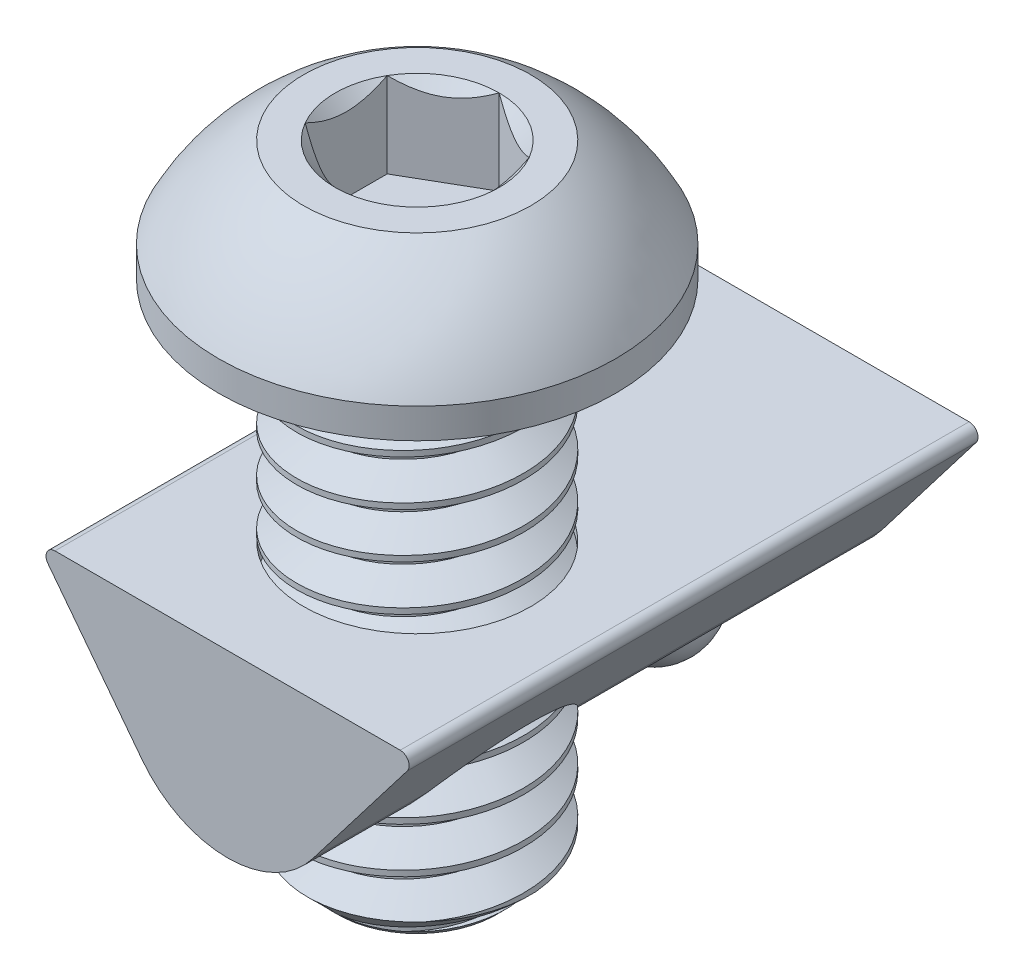
SolidWorks part; units mm, degrees
ref_plane "Front Plane" through (0, 0, 0) normal (0, 0, 1) x (1, 0, 0)
ref_plane "Top Plane" through (0, 0, 0) normal (0, 1, 0) x (1, 0, 0)
ref_plane "Right Plane" through (0, 0, 0) normal (1, 0, 0) x (0, 0, -1)
sketch "Sketch1" plane through (0, 0, 0) normal (0, 1, 0) x (1, 0, 0)
  circle A0 centre (0, 0) radius 3.175
  point P2 (3.175, 0)
  point P3 (-3.175, 0)
  dimension "D1" = 6.35
extrude "Boss-Extrude1" add sketch "Sketch1" against normal blind 14.2875
sketch "Sketch2" plane through (0, -14.2875, 0) normal (0, -1, 0) x (1, 0, 0)
  circle A1 centre (0, 0) radius 3.175
  circle A2 centre (0, 0) radius 3.175
  point P0 (0, -3.175)
  dimension "D1" = 0
curve "Helix/Spiral1" pitch 1.27 height 15.5575 turns 12.25
sketch "Sketch3" plane through (0, 0, 0) normal (1, 0, 0) x (0, 0, -1)
  line L0 (3.3125, -14.2081) -> (2.2126, -14.8431) construction
  line L1 (2.2126, -14.8431) -> (3.3125, -15.4781) construction
  line L2 (3.3125, -15.4781) -> (3.3125, -14.2081) construction
  line L3 (2.3501, -14.7637) -> (2.3501, -14.9225) construction
  line L4 (3.175, -14.2875) -> (3.175, -15.3987) construction
  line L5 (2.2126, -14.8431) -> (2.3501, -14.8431) construction
  line L6 (3.175, -14.8431) -> (3.3125, -14.8431) construction
  line L8 (2.2126, -14.8431) -> (-3.175, -14.8431) construction
  line L9 (2.3501, -14.7637) -> (3.2437, -14.2478)
  line L10 (2.3501, -14.7637) -> (2.3501, -14.9225)
  line L11 (2.3501, -14.9225) -> (3.2437, -15.4384)
  line L12 (3.2437, -15.4384) -> (3.2437, -14.2478)
  line L14 (-3.175, -14.8431) -> (-3.175, -13.5731) construction
  line L15 (-3.175, -13.5731) -> (-3.175, -12.3031) construction
  line L16 (-3.175, -12.3031) -> (-3.175, -11.0331) construction
  line L17 (-3.175, -11.0331) -> (-3.175, -9.7631) construction
  line L18 (-3.175, 0) -> (-3.175, -14.2875) construction
  point P15 (3.2437, -14.8431)
  dimension "D1" = 1.27
  dimension "D2" = 0.1588
sweep "Cut-Sweep1" cut profiles "Sketch3" path "Helix/Spiral1" align with end faces yes
sketch "SketchZ" plane through (0, 0, 0) normal (0, 0, 1) x (1, 0, 0)
  line L0 (0, -14.8431) -> (0, -14.2081) construction
  line L1 (0, -14.5256) -> (3.175, -14.5256) construction
  line L2 (3.175, -14.5256) -> (3.175, -13.2556) construction
  line L3 (0, -14.8431) -> (0, -13.5731) construction
sketch "Sketch4" plane through (0, -14.2875, 0) normal (0, -1, 0) x (1, 0, 0)
  circle A0 centre (0, 0) radius 2.2126
extrude "Cut-Extrude1" cut sketch "Sketch4" against normal blind 1.27 draft 45 flip side to cut
sketch "Sketch5" plane through (0, 0, 0) normal (0, 0, 1) x (1, 0, 0)
  line L0 (0, 3.3528) -> (0, 0)
  line L1 (0, 0) -> (-7.112, 0) construction
  line L2 (0, 3.3528) -> (-3.175, 3.3528)
  line L3 (-7.112, 0) -> (-7.112, 0.8382) construction
  line L4 (-7.112, 0.8382) -> (-5.5499, 0.8382) construction
  line L5 (0, 0) -> (0, -13.9857) construction
  line L6 (-5.5499, 0.8382) -> (-5.5499, 0)
  line L7 (-5.5499, 0) -> (0, 0)
  arc A0 (-5.5499, 0.8382) -> (-3.175, 3.3528) centre (0, -2.0246) cw
  dimension "D1" = 11.0998
  dimension "D2" = 7.112
  dimension "D3" = 3.3528
  dimension "D4" = 0.8382
revolve "Revolve1" add sketch "Sketch5" angle 360 mid plane about L5
sketch "Sketch6" plane through (0, 3.3528, 0) normal (0, 1, 0) x (1, 0, 0)
  line L1 (0, 2.2914) -> (-1.9844, 1.1457)
  line L2 (-1.9844, 1.1457) -> (-1.9844, -1.1457)
  line L3 (-1.9844, -1.1457) -> (0, -2.2914)
  line L4 (0, -2.2914) -> (1.9844, -1.1457)
  line L5 (1.9844, -1.1457) -> (1.9844, 1.1457)
  line L6 (1.9844, 1.1457) -> (0, 2.2914)
  circle A0 centre (0, 0) radius 1.9844 construction
extrude "Cut-Extrude2" cut sketch "Sketch6" against normal blind 2.3813
sketch "Sketch7" plane through (0, 3.3528, 0) normal (0, 1, 0) x (1, 0, 0)
  circle A0 centre (0, 0) radius 2.2914
extrude "Cut-Extrude3" cut sketch "Sketch7" against normal blind 2.3813 draft 45
sketch "Sketch8" plane through (0, 0, 0) normal (0, 0, 1) x (1, 0, 0)
  line L0 (5.075, -6.35) -> (5.075, -11.3707) construction
  line L4 (5.075, -11.3707) -> (-5.075, -11.3707) construction
  line L7 (-5.075, -6.35) -> (5.075, -6.35) construction
  line L10 (0, 0) -> (0, -6.35) construction
  line L11 (-5.075, -11.3707) -> (-5.075, -6.35) construction
  line L12 (-5.0233, -6.7522) -> (-2.3801, -10.197)
  line L13 (-4.825, -6.35) -> (4.825, -6.35)
  line L14 (5.0233, -6.7522) -> (2.3801, -10.197)
  line L18 (0, -6.35) -> (0, -11.3707) construction
  arc A1 (-2.3801, -10.197) -> (2.3801, -10.197) centre (0, -8.3707) ccw
  arc A2 (-4.825, -6.35) -> (-5.0233, -6.7522) centre (-4.825, -6.6) ccw
  arc A3 (4.825, -6.35) -> (5.0233, -6.7522) centre (4.825, -6.6) cw
  dimension "D1" = 10.15
  dimension "D3" = 75
  dimension "D4" = 3
  dimension "D6" = 0.25
  dimension "D2" = 6.35
  dimension "D5" = 5.0207
extrude "Boss-Extrude2" add sketch "Sketch8" against normal blind 15.9 from offset 5.3 separate body
sketch "Sketch9" plane through (0, 0, 0) normal (0, 1, 0) x (1, 0, 0)
  circle A2 centre (0, 0) radius 3.175
  circle A3 centre (0, 0) radius 3.175
  dimension "D2" = 0
extrude "Cut-Extrude4" cut sketch "Sketch9" against normal through all
sketch "Sketch10" plane through (0, 0, 0) normal (1, 0, 0) x (0, 0, -1)
  line L0 (6.6, -6.35) -> (6.6, -6.6) construction
  line L1 (10.6, -6.35) -> (-5.3, -6.35) construction
  line L2 (6.6, -6.6) -> (6.6, -11.3707)
  line L3 (3.175, -11.3707) -> (10.6, -11.3707) construction
  line L4 (6.6, -11.3707) -> (5.1, -11.3707)
  line L5 (3.175, -11.3707) -> (10.6, -11.3707) construction
  line L6 (5.1, -11.3707) -> (5.1, -7.35)
  line L7 (5.1, -7.35) -> (6.399, -6.6)
  line L8 (6.399, -6.6) -> (6.6, -6.6)
  dimension "D1" = 6.6
  dimension "D2" = 3
  dimension "D3" = 0.25
  dimension "D4" = 60
  dimension "D5" = 0.75
revolve "Cut-Revolve1" cut sketch "Sketch10" angle 360 mid plane about L0
sketch "Sketch11" plane through (0, 0, 0) normal (1, 0, 0) x (0, 0, -1)
  line L0 (6.6, -6.6) -> (6.6, -11.3707) construction
  line L1 (6.6, -9.3707) -> (6.6, -12.3707)
  line L2 (8.1, -11.3707) -> (10.6, -11.3707) construction
  line L3 (5.1, -11.3707) -> (5.1, -7.35) construction
  arc A0 (6.6, -9.3707) -> (6.6, -12.3707) centre (6.6, -10.8707) ccw
  dimension "D1" = 1
revolve "Revolve2" add sketch "Sketch11" angle 360 mid plane about L1
equation "\"D3@Helix/Spiral1\" = \"D4@Helix/Spiral1\" + \"D1@Boss-Extrude1\""
equation "\"D1@Sketch3\" = \"D4@Helix/Spiral1\""
equation "\"D2@Sketch3\" = \"D1@Sketch3\" / 8"
equation "\"D1@Cut-Extrude1\" = \"D4@Helix/Spiral1\""
equation "\"D1@Cut-Extrude2\" = \"D1@Sketch6\" * 3/5"
equation "\"D1@Cut-Extrude3\" = \"D1@Cut-Extrude2\""
equation "\"D4@Sketch5\" = \"D3@Sketch5\" * 1/4"
